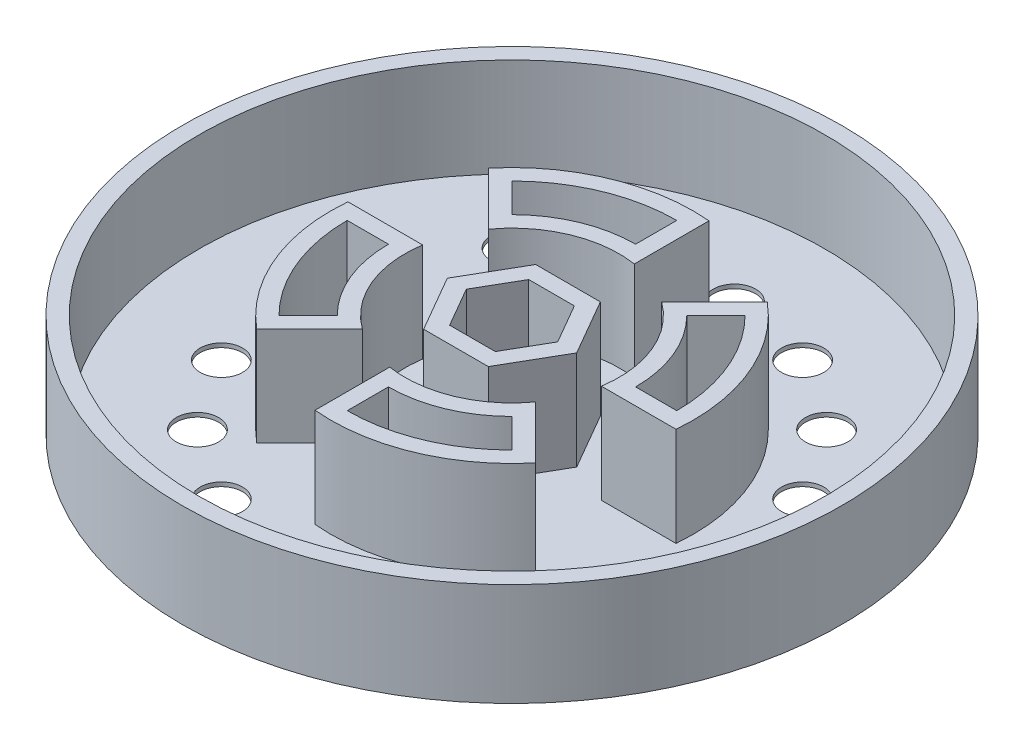
SolidWorks part; units mm, degrees
ref_plane "Front Plane" through (0, 0, 0) normal (0, 0, 1) x (1, 0, 0)
ref_plane "Top Plane" through (0, 0, 0) normal (0, 1, 0) x (1, 0, 0)
ref_plane "Right Plane" through (0, 0, 0) normal (1, 0, 0) x (0, 0, -1)
sketch "Sketch1" plane through (0, 0, 0) normal (0, 1, 0) x (1, 0, 0)
  circle A0 centre (0, 0) radius 50.8
  dimension "D1" = 101.6
extrude "Boss-Extrude1" add sketch "Sketch1" along normal blind 15.875
sketch "Sketch4" plane through (0, 15.875, 0) normal (0, 1, 0) x (1, 0, 0)
  line L0 (-3.5195, 6.096) -> (3.5195, 6.096)
  line L1 (3.5195, 6.096) -> (7.0391, 0)
  line L2 (7.0391, 0) -> (3.5195, -6.096)
  line L3 (3.5195, -6.096) -> (-3.5195, -6.096)
  line L4 (-3.5195, -6.096) -> (-7.0391, 0)
  line L5 (-7.0391, 0) -> (-3.5195, 6.096)
  point P7 (0, 6.096)
  dimension "D1" = 120
  dimension "D2" = 12.192
extrude "Hex hole" cut sketch "Sketch4" against normal blind 15.24 contours L5 L0 L1 L2 L3 L4
sketch "Sketch5" plane through (0, 0.635, 0) normal (0, 1, 0) x (1, 0, 0)
  circle A0 centre (0, 0) radius 4.191
  dimension "D1" = 8.382
extrude "Centerhole" cut sketch "Sketch5" against normal through all contours A0
sketch "Sketch6" plane through (0, 15.875, 0) normal (0, 1, 0) x (1, 0, 0)
  line L0 (0, 0) -> (0, 25.4)
  line L1 (0, 0) -> (17.9605, 17.9605)
  line L2 (0, 0) -> (25.4, 0)
  line L3 (0, 0) -> (17.9605, -17.9605)
  line L4 (0, 0) -> (0, -25.4)
  line L5 (0, 0) -> (-17.9605, -17.9605)
  line L6 (0, 0) -> (-25.4, 0)
  line L7 (0, 0) -> (-17.9605, 17.9605)
  circle A0 centre (0, 0) radius 25.4
  circle A1 centre (0, 0) radius 19.05
  point P15 (0, 0)
  dimension "D1" = 38.1
  dimension "D2" = 50.8
  dimension "D3" = 45
  dimension "D4" = 4
extrude "weight loss" cut sketch "Sketch6" against normal through all contours A1 L0 A0 L7 | A1 L2 A0 L1 | A1 L4 A0 L3 | A1 L6 A0 L5 region at (-8.3446, 15.875, -20.1456) region at (20.1456, 15.875, -8.3446) region at (8.3446, 15.875, 20.1456) region at (-20.1456, 15.875, 8.3446)
sketch "Sketch7" plane through (0, 15.875, 0) normal (0, 1, 0) x (1, 0, 0)
  line L27 (16.3134, -2.54) -> (27.8243, -2.54)
  line L28 (17.8787, 21.4708) -> (9.7393, 13.3314)
  line L29 (2.54, 16.3134) -> (2.54, 27.8243)
  line L30 (-21.4708, 17.8787) -> (-13.3314, 9.7393)
  line L31 (2.54, 16.3134) -> (2.54, 27.8243)
  line L32 (-21.4708, 17.8787) -> (-13.3314, 9.7393)
  line L33 (-2.54, -16.3134) -> (-2.54, -27.8243)
  line L34 (21.4708, -17.8787) -> (13.3314, -9.7393)
  line L35 (-16.3134, 2.54) -> (-27.8243, 2.54)
  line L36 (-17.8787, -21.4708) -> (-9.7393, -13.3314)
  line L64 (9.972, 0) -> (4.986, 8.636)
  line L65 (4.986, -8.636) -> (9.972, 0)
  line L66 (-4.986, -8.636) -> (4.986, -8.636)
  line L67 (-9.972, 0) -> (-4.986, -8.636)
  line L68 (-4.986, 8.636) -> (-9.972, 0)
  line L69 (4.986, 8.636) -> (-4.986, 8.636)
  line L70 (9.972, 0) -> (4.986, 8.636)
  line L71 (4.986, -8.636) -> (9.972, 0)
  line L72 (-4.986, -8.636) -> (4.986, -8.636)
  line L73 (-9.972, 0) -> (-4.986, -8.636)
  line L74 (-4.986, 8.636) -> (-9.972, 0)
  line L75 (4.986, 8.636) -> (-4.986, 8.636)
  arc A28 (27.8243, -2.54) -> (17.8787, 21.4708) centre (0, 0) ccw
  arc A29 (16.3134, -2.54) -> (9.7393, 13.3314) centre (0, 0) ccw
  arc A30 (2.54, 16.3134) -> (-13.3314, 9.7393) centre (0, 0) ccw
  arc A31 (2.54, 27.8243) -> (-21.4708, 17.8787) centre (0, 0) ccw
  arc A32 (2.54, 16.3134) -> (-13.3314, 9.7393) centre (0, 0) ccw
  arc A33 (2.54, 27.8243) -> (-21.4708, 17.8787) centre (0, 0) ccw
  arc A34 (-2.54, -27.8243) -> (21.4708, -17.8787) centre (0, 0) ccw
  arc A35 (-2.54, -16.3134) -> (13.3314, -9.7393) centre (0, 0) ccw
  arc A36 (-27.8243, 2.54) -> (-17.8787, -21.4708) centre (0, 0) ccw
  arc A37 (-16.3134, 2.54) -> (-9.7393, -13.3314) centre (0, 0) ccw
  circle A40 centre (0, 0) radius 48.26
  circle A41 centre (0, 0) radius 50.8 construction
  point P15 (0, 0)
  dimension "D4" = 2.54
  dimension "D1" = 2.54
  dimension "D3" = 2.54
  dimension "D2" = 4
extrude "Hollow out" cut sketch "Sketch7" against normal up to surface (15.24 mm away) contours A40 L35 A37 L36 A36 L27 A29 L28 A28 L75 L70 L71 L72 L73 L74 A33 L31 A32 L32 L33 A35 L34 A34 region at (-46.895, 15.875, 0) up to face at (0, 0.635, 4.191)
sketch "Sketch8" plane through (0, 0, 0) normal (0, -1, 0) x (1, 0, 0)
  line L0 (0, 0) -> (0, 25.4) construction
  line L1 (0, 0) -> (-17.9605, 17.9605) construction
  line L2 (-13.1222, 31.6798) -> (0, 0) construction
  circle A0 centre (-13.1222, 31.6798) radius 3.2639
  circle A4 centre (0, 34.29) radius 3.2639
  circle A5 centre (13.1222, 31.6798) radius 3.2639
  circle A6 centre (24.2467, 24.2467) radius 3.2639
  circle A7 centre (31.6798, 13.1222) radius 3.2639
  circle A8 centre (34.29, 0) radius 3.2639
  circle A9 centre (31.6798, -13.1222) radius 3.2639
  circle A10 centre (24.2467, -24.2467) radius 3.2639
  circle A11 centre (13.1222, -31.6798) radius 3.2639
  circle A12 centre (0, -34.29) radius 3.2639
  circle A13 centre (-13.1222, -31.6798) radius 3.2639
  circle A14 centre (-24.2467, -24.2467) radius 3.2639
  circle A15 centre (-31.6798, -13.1222) radius 3.2639
  circle A16 centre (-34.29, 0) radius 3.2639
  circle A17 centre (-31.6798, 13.1222) radius 3.2639
  circle A18 centre (-24.2467, 24.2467) radius 3.2639
  point P17 (0, 0)
  dimension "D1" = 6.5278
  dimension "D2" = 22.5
  dimension "D3" = 34.29
  dimension "D4" = 16
extrude "outside screw holes" cut sketch "Sketch8" against normal through all contours A6 | A4 | A5 | A7 | A8 | A9 | A10 | A11 | A12 | A13 | A14 | A15 | A16 | A17 | A18 | A0 region at (0, 0, 34.29) region at (13.1222, 0, 31.6798) region at (24.2467, 0, 24.2467) region at (31.6798, 0, 13.1222) region at (34.29, 0, 0) region at (31.6798, 0, -13.1222) region at (24.2467, 0, -24.2467) region at (13.1222, 0, -31.6798) region at (0, 0, -34.29) region at (-13.1222, 0, -31.6798) region at (-24.2467, 0, -24.2467) region at (-31.6798, 0, -13.1222) region at (-34.29, 0, 0) region at (-31.6798, 0, 13.1222) region at (-24.2467, 0, 24.2467)
